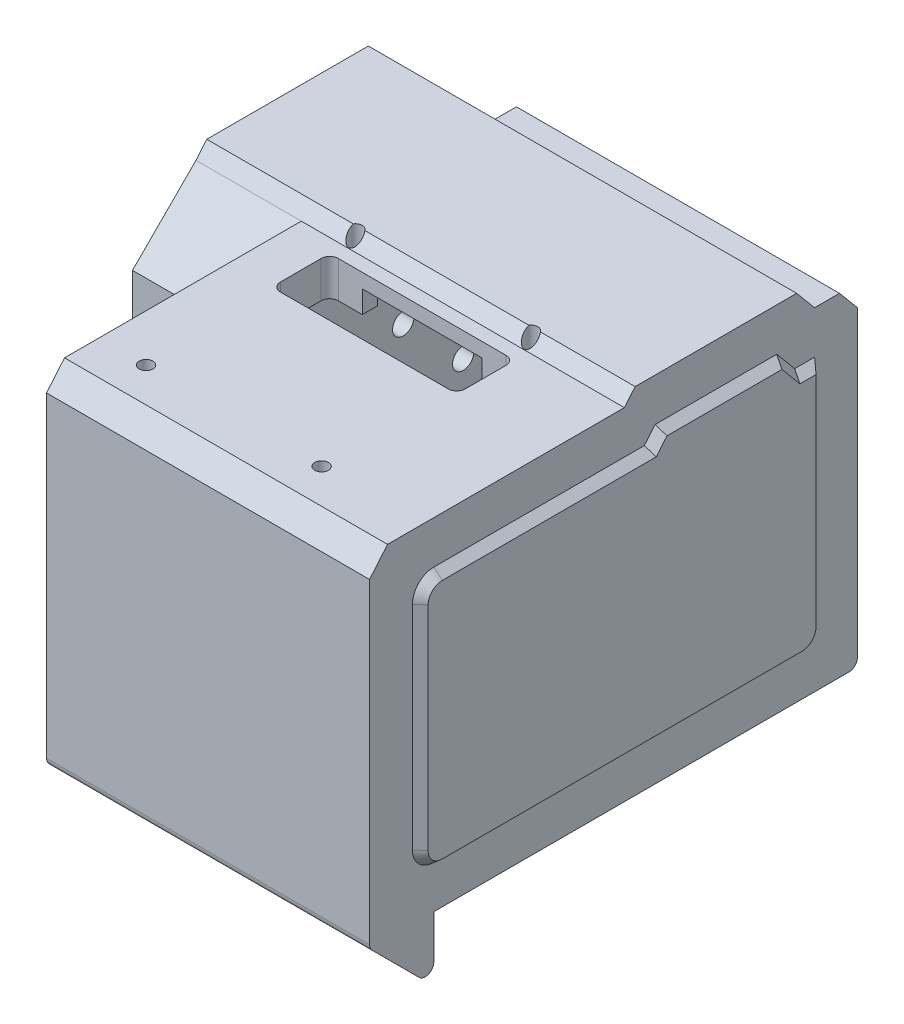
SolidWorks part; units mm, degrees
material "PLA"
ref_plane "Front Plane" through (0, 0, 0) normal (0, 0, 1) x (1, 0, 0)
ref_plane "Top Plane" through (0, 0, 0) normal (0, 1, 0) x (1, 0, 0)
ref_plane "Right Plane" through (0, 0, 0) normal (1, 0, 0) x (0, 0, -1)
sketch "Sketch1" plane through (0, 0, 0) normal (1, 0, 0) x (0, 0, -1)
  line L0 (-25.985, 0) -> (25.985, 0) construction
  line L1 (0, 21.625) -> (0, -21.625) construction
  line L7 (-25.985, -21.625) -> (25.985, -21.625)
  line L8 (-25.985, -21.625) -> (-25.985, 21.625)
  line L9 (-25.985, 21.625) -> (25.985, 21.625)
  line L10 (25.985, -21.625) -> (25.985, 21.625)
  point P5 (0, 0)
  dimension "D1" = 51.97
  dimension "D2" = 43.25
extrude "Boss-Extrude1" add sketch "Sketch1" along normal blind 3.175
sketch "Sketch2" plane through (3.175, 0, 0) normal (1, 0, 0) x (0, 0, -1)
  line L8 (-22.81, 18.45) -> (-22.81, -18.45)
  line L9 (-22.81, -18.45) -> (22.81, -18.45)
  line L10 (22.81, -18.45) -> (22.81, 18.45)
  line L11 (22.81, 18.45) -> (-22.81, 18.45)
  line L12 (-22.81, 18.45) -> (-22.81, -18.45)
  line L13 (-22.81, -18.45) -> (22.81, -18.45)
  line L14 (22.81, -18.45) -> (22.81, 18.45)
  line L15 (22.81, 18.45) -> (-22.81, 18.45)
  line L16 (-25.985, 21.625) -> (-25.985, -21.625)
  line L17 (-25.985, -21.625) -> (25.985, -21.625)
  line L18 (25.985, -21.625) -> (25.985, 21.625)
  line L19 (25.985, 21.625) -> (-25.985, 21.625)
  line L20 (-25.985, 21.625) -> (-25.985, -21.625)
  line L21 (-25.985, -21.625) -> (25.985, -21.625)
  line L22 (25.985, -21.625) -> (25.985, 21.625)
  line L23 (25.985, 21.625) -> (-25.985, 21.625)
  dimension "D1" = 3.175
  dimension "D2" = 0
extrude "Boss-Extrude2" add sketch "Sketch2" along normal blind 25.12
sketch "Sketch5" plane through (0, 18.45, 0) normal (0, -1, 0) x (1, 0, 0)
  line L0 (6.0285, -6.9385) -> (3.175, -6.9385)
  line L1 (25.4415, -6.9385) -> (28.295, -6.9385)
  line L4 (3.175, 22.81) -> (3.175, -22.81)
  line L5 (3.175, -22.81) -> (28.295, -22.81)
  line L6 (28.295, -22.81) -> (28.295, 22.81)
  line L7 (28.295, 22.81) -> (3.175, 22.81)
  line L8 (3.175, 22.81) -> (3.175, -6.9385)
  line L10 (28.295, -6.9385) -> (28.295, 22.81)
  line L11 (28.295, 22.81) -> (3.175, 22.81)
  line L36 (26.535, -2.15) -> (22.735, -2.15)
  line L37 (26.535, 4.625) -> (26.535, -2.15)
  line L38 (25.038, 4.625) -> (26.535, 4.625)
  line L39 (25.1773, 4.8479) -> (25.038, 4.625)
  line L40 (25.1773, 15.8031) -> (25.1773, 4.8479)
  line L41 (7.4927, 17.0031) -> (23.9773, 17.0031)
  line L42 (6.2927, 4.8479) -> (6.2927, 15.8031)
  line L43 (6.432, 4.625) -> (6.2927, 4.8479)
  line L44 (4.935, 4.625) -> (6.432, 4.625)
  line L45 (4.935, -2.15) -> (4.935, 4.625)
  line L46 (8.735, -2.15) -> (4.935, -2.15)
  line L47 (8.735, -3.9136) -> (8.735, -2.15)
  line L48 (4.375, -6.9385) -> (6.0285, -6.9385)
  line L49 (3.875, 20.2102) -> (3.875, -6.4385)
  line L50 (26.0951, 21.71) -> (5.3746, 21.71)
  line L51 (27.595, -6.4385) -> (27.595, 20.2105)
  line L52 (25.4415, -6.9385) -> (27.095, -6.9385)
  line L53 (22.735, -2.15) -> (22.735, -3.9136)
  line L54 (26.535, -2.15) -> (22.735, -2.15)
  line L55 (26.535, 4.625) -> (26.535, -2.15)
  line L56 (25.038, 4.625) -> (26.535, 4.625)
  line L57 (25.1773, 4.8479) -> (25.038, 4.625)
  line L58 (25.1773, 15.8031) -> (25.1773, 4.8479)
  line L59 (7.4927, 17.0031) -> (23.9773, 17.0031)
  line L60 (6.2927, 4.8479) -> (6.2927, 15.8031)
  line L61 (6.432, 4.625) -> (6.2927, 4.8479)
  line L62 (4.935, 4.625) -> (6.432, 4.625)
  line L63 (4.935, -2.15) -> (4.935, 4.625)
  line L64 (8.735, -2.15) -> (4.935, -2.15)
  line L65 (8.735, -3.9136) -> (8.735, -2.15)
  line L71 (22.735, -2.15) -> (22.735, -3.9136)
  arc A12 (25.1773, 15.8031) -> (23.9773, 17.0031) centre (23.9773, 15.8031) ccw
  arc A13 (7.4927, 17.0031) -> (6.2927, 15.8031) centre (7.4927, 15.8031) ccw
  arc A14 (8.735, -3.9136) -> (6.0285, -6.9385) centre (15.735, -12.9) ccw
  arc A15 (3.875, -6.4385) -> (4.375, -6.9385) centre (4.375, -6.4385) ccw
  arc A16 (27.095, -6.9385) -> (27.595, -6.4385) centre (27.095, -6.4385) ccw
  arc A17 (25.4415, -6.9385) -> (22.735, -3.9136) centre (15.735, -12.9) ccw
  arc A18 (25.1773, 15.8031) -> (23.9773, 17.0031) centre (23.9773, 15.8031) ccw
  arc A19 (7.4927, 17.0031) -> (6.2927, 15.8031) centre (7.4927, 15.8031) ccw
  arc A20 (8.735, -3.9136) -> (6.0285, -6.9385) centre (15.735, -12.9) ccw
  arc A23 (25.4415, -6.9385) -> (22.735, -3.9136) centre (15.735, -12.9) ccw
  circle A68 centre (5.485, -4.6) radius 0.8
  circle A69 centre (5.485, 19.85) radius 0.8
  circle A70 centre (25.985, 19.85) radius 0.8
  circle A71 centre (25.985, -4.6) radius 0.8
  spline S4 degree 3 poles (199.8506, -959.1962) (36.727, -55.2614) (14.0519, 23.473) (4.9866, 21.6619) (4.8913, 21.6332) (4.7098, 21.558) (4.6238, 21.5118) (4.4608, 21.403) (4.3836, 21.3399) (4.1763, 21.1325) (4.0645, 20.9654) (1.0086, 13.5957) (53.0588, -19.6485) (521.6785, 875.7094) knots -11.579327 -11.579327 -11.579327 -11.579327 0.125 0.125 0.25 0.25 0.375 0.375 0.5 0.5 0.75 0.75 10.719736 10.719736 10.719736 10.719736 only from (5.3746, 21.71) to (3.875, 20.2102)
  spline S5 degree 3 poles (-953.307, -174.2909) (-49.38, -11.1451) (29.3583, 11.5329) (27.5469, 20.5985) (27.5181, 20.6937) (27.443, 20.8752) (27.3968, 20.9612) (27.288, 21.1242) (27.2248, 21.2014) (27.0175, 21.4088) (26.8503, 21.5206) (19.4805, 24.5762) (-13.7629, -27.4761) (881.6326, -496.0119) knots -11.579675 -11.579675 -11.579675 -11.579675 0.125 0.125 0.25 0.25 0.375 0.375 0.5 0.5 0.75 0.75 10.719832 10.719832 10.719832 10.719832 only from (27.595, 20.2105) to (26.0951, 21.71)
  dimension "D3" = 1.6
  dimension "D1" = 0.2
  dimension "D2" = 0
extrude "Boss-Extrude4" add sketch "Sketch5" along normal blind 2.6
sketch "Sketch6" plane through (0, 18.45, 0) normal (0, -1, 0) x (1, 0, 0)
  line L1 (4.935, 4.625) -> (26.535, 4.625)
  line L2 (4.935, 4.625) -> (4.935, -2.15)
  line L3 (4.935, -2.15) -> (26.535, -2.15)
  line L4 (26.535, 4.625) -> (26.535, -2.15)
  line L18 (6.0285, -6.9385) -> (3.175, -6.9385)
  line L19 (3.175, -6.9385) -> (3.175, -22.81)
  line L20 (3.175, -22.81) -> (28.295, -22.81)
  line L21 (28.295, -22.81) -> (28.295, -6.9385)
  line L22 (28.295, -6.9385) -> (25.4415, -6.9385)
  line L23 (22.735, -3.9136) -> (22.735, -2.15)
  line L24 (22.735, -2.15) -> (26.535, -2.15)
  line L25 (26.535, -2.15) -> (26.535, 4.625)
  line L26 (26.535, 4.625) -> (25.038, 4.625)
  line L27 (25.038, 4.625) -> (25.1773, 4.8479)
  line L28 (25.1773, 4.8479) -> (25.1773, 15.8031)
  line L29 (23.9773, 17.0031) -> (7.4927, 17.0031)
  line L30 (6.2927, 15.8031) -> (6.2927, 4.8479)
  line L31 (6.2927, 4.8479) -> (6.432, 4.625)
  line L32 (6.432, 4.625) -> (4.935, 4.625)
  line L33 (4.935, 4.625) -> (4.935, -2.15)
  line L34 (4.935, -2.15) -> (8.735, -2.15)
  line L35 (8.735, -2.15) -> (8.735, -3.9136)
  line L42 (22.735, -2.15) -> (26.535, -2.15)
  line L43 (26.535, -2.15) -> (26.535, 4.625)
  line L44 (26.535, 4.625) -> (25.038, 4.625)
  line L50 (6.432, 4.625) -> (4.935, 4.625)
  line L51 (4.935, 4.625) -> (4.935, -2.15)
  line L52 (4.935, -2.15) -> (8.735, -2.15)
  arc A4 (8.735, -3.9136) -> (6.0285, -6.9385) centre (15.735, -12.9) ccw
  arc A5 (25.4415, -6.9385) -> (22.735, -3.9136) centre (15.735, -12.9) ccw
  arc A6 (25.1773, 15.8031) -> (23.9773, 17.0031) centre (23.9773, 15.8031) ccw
  arc A7 (7.4927, 17.0031) -> (6.2927, 15.8031) centre (7.4927, 15.8031) ccw
  line M35 (22.735, -2.15) -> (26.535, -2.15)
  line M36 (26.535, -2.15) -> (26.535, 4.625)
  line M37 (26.535, 4.625) -> (25.038, 4.625)
  line M45 (6.432, 4.625) -> (4.935, 4.625)
  line M46 (4.935, 4.625) -> (4.935, -2.15)
  line M47 (4.935, -2.15) -> (8.735, -2.15)
  dimension "D1" = 0
extrude "Cut-Extrude2" cut sketch "Sketch6" against normal through all contours L3 L1 M47 M35 M36 M37 M45 M46 region at (15.735, 18.45, 1.2375)
fillet "Fillet4" radius 1 4 edges at (26.535, 18.7375, -2.15) (26.535, 18.7375, 4.625) (4.935, 18.7375, -2.15) (4.935, 18.7375, 4.625)
sketch "Sketch7" plane through (0, 21.625, 0) normal (0, 1, 0) x (1, 0, 0)
  line L0 (28.295, 25.985) -> (28.295, -25.985) construction
  line L1 (0, -25.985) -> (28.295, -25.985)
  line L2 (0, -25.985) -> (0, 3.765)
  line L3 (0, 3.765) -> (28.295, 3.765)
  line L4 (28.295, -25.985) -> (28.295, 3.765)
  line M5 (25.535, -4.625) -> (5.935, -4.625)
  arc M6 (5.935, -4.625) -> (4.935, -3.625) centre (5.935, -3.625) cw
  line M7 (4.935, -3.625) -> (4.935, 1.15)
  arc M8 (4.935, 1.15) -> (5.935, 2.15) centre (5.935, 1.15) cw
  line M9 (5.935, 2.15) -> (25.535, 2.15)
  arc M10 (25.535, 2.15) -> (26.535, 1.15) centre (25.535, 1.15) cw
  line M11 (26.535, 1.15) -> (26.535, -3.625)
  arc M12 (26.535, -3.625) -> (25.535, -4.625) centre (25.535, -3.625) cw
  line M13 (0, 25.985) -> (0, -25.985)
  line M14 (0, -25.985) -> (28.295, -25.985)
  line M15 (28.295, -25.985) -> (28.295, 25.985)
  dimension "D1" = 29.75
extrude "Cut-Extrude3" cut sketch "Sketch7" against normal blind 1.5 contours L3 M13 M14 M15 M12 M5 M6 M7 M8 M9 M10 M11 region at (13.8158, 21.625, 13.1727)
chamfer "Chamfer3" distance 1.5 angle 40 1 edges at (14.1475, 21.625, -3.765) first distance on face at (14.1475, 20.875, -3.765)
chamfer "Chamfer4" distance 2.5 angle 40 1 edges at (14.1475, 20.125, 25.985) first distance on face at (14.1475, -0.75, 25.985)
chamfer "Chamfer5" distance 2.5 angle 40 1 edges at (14.1475, 21.625, -25.985) first distance on face at (14.1475, 0, -25.985)
sketch "Sketch8" plane through (0, -18.45, 0) normal (0, 1, 0) x (1, 0, 0)
  line L1 (8.535, 2.2774) -> (8.535, -21.2062)
  line L6 (22.935, -21.2062) -> (22.935, 2.2774)
  line L8 (5.6661, 6.9407) -> (3.175, 6.9407)
  line L11 (25.803, 6.9392) -> (28.295, 6.9392)
  line L16 (8.8158, -21.9777) -> (8.8158, -22.81)
  line L18 (22.6542, -21.9776) -> (22.6542, -22.81)
  line L19 (3.175, 22.81) -> (3.175, -22.81)
  line L20 (3.175, -22.81) -> (28.295, -22.81)
  line L21 (28.295, -22.81) -> (28.295, 22.81)
  line L22 (28.295, 22.81) -> (3.175, 22.81)
  line L23 (3.175, 6.9407) -> (3.175, -22.81)
  line L24 (3.175, -22.81) -> (8.8158, -22.81)
  line L25 (28.295, -22.81) -> (28.295, 6.9392)
  line L27 (22.6542, -22.81) -> (28.295, -22.81)
  arc A6 (5.6661, 6.9407) -> (9.0755, 3.2799) centre (15.735, 12.9) ccw
  arc A9 (9.0755, 3.2799) -> (8.535, 2.2774) centre (9.735, 2.2774) ccw
  arc A20 (8.535, -21.2062) -> (8.8158, -21.9777) centre (9.735, -21.2062) ccw
  arc A23 (22.6542, -21.9776) -> (22.935, -21.2062) centre (21.735, -21.2062) ccw
  arc A28 (22.935, 2.2774) -> (22.3945, 3.2799) centre (21.735, 2.2774) ccw
  arc A35 (22.3945, 3.2799) -> (25.803, 6.9392) centre (15.735, 12.9) ccw
  circle A56 centre (25.985, -16.1) radius 0.8
  circle A57 centre (5.485, 4.6) radius 0.8
  circle A58 centre (25.985, 4.6) radius 0.8
  circle A59 centre (5.485, -16.1) radius 0.8
  spline S5 degree 3 poles (5.6659, 6.9385) (5.666, 6.9385) (5.6664, 6.9383) (5.6671, 6.938) (5.6678, 6.9375) (5.6681, 6.9373) (5.6683, 6.9372) knots 0.329528 0.329528 0.329528 0.329528 0.414347 0.499166 0.583985 0.668804 0.668804 0.668804 0.668804
  line M1 (3.175, 22.81) -> (3.175, -22.81)
  line M2 (3.175, -22.81) -> (28.295, -22.81)
  line M3 (28.295, -22.81) -> (28.295, 22.81)
  dimension "D1" = 1.6
  dimension "D2" = 1.6
  dimension "D3" = 1.6
  dimension "D4" = 1.6
  dimension "D5" = 0
extrude "Boss-Extrude5" add sketch "Sketch8" along normal blind 1.9 contours A20 L1 A9 A6 L8 L16 A59 A57 M1 M2 | A35 A28 L6 A23 L18 L11 A58 A56 M2 M3 region at (5.8173, -18.45, 8.4819) region at (25.6526, -18.45, 8.4823)
sketch "Sketch9" plane through (0, 18.45, 0) normal (0, -1, 0) x (1, 0, 0)
  circle A0 centre (5.485, -4.6) radius 0.8 construction
  circle A1 centre (25.985, -4.6) radius 0.8 construction
  circle A2 centre (25.985, 19.85) radius 0.8 construction
  circle A3 centre (5.485, 19.85) radius 0.8 construction
  circle A4 centre (5.485, -4.6) radius 0.8
  circle A5 centre (25.985, -4.6) radius 0.8
  circle A6 centre (25.985, 19.85) radius 0.8
  circle A7 centre (5.485, 19.85) radius 0.8
extrude "Cut-Extrude4" cut sketch "Sketch9" against normal through all
sketch "Sketch10" plane through (0, -21.625, 0) normal (0, -1, 0) x (1, 0, 0)
  line L0 (28.295, 25.985) -> (28.295, -25.985) construction
  line L1 (0, 25.985) -> (28.295, 25.985)
  line L2 (0, 25.985) -> (0, -6.935)
  line L3 (0, -6.935) -> (28.295, -6.935)
  line L4 (28.295, 25.985) -> (28.295, -6.935)
  dimension "D1" = 32.92
extrude "Cut-Extrude5" cut sketch "Sketch10" against normal blind 1.9
chamfer "Chamfer6" distance 1.9 angle 40 1 edges at (14.1475, -19.725, -6.935) first distance on face at (14.1475, -20.675, -6.935)
sketch "Sketch11" plane through (0, -18.45, 0) normal (0, 1, 0) x (1, 0, 0)
  line L10 (3.175, 22.81) -> (3.175, 6.9407)
  line L11 (3.175, 6.9407) -> (5.6661, 6.9407)
  line L12 (8.535, 2.2774) -> (8.535, -21.2062)
  line L13 (8.8158, -21.9777) -> (8.8158, -22.81)
  line L14 (8.8158, -22.81) -> (22.6542, -22.81)
  line L15 (22.6542, -22.81) -> (22.6542, -21.9776)
  line L16 (22.935, -21.2062) -> (22.935, 2.2774)
  line L17 (25.803, 6.9392) -> (28.295, 6.9392)
  line L18 (28.295, 6.9392) -> (28.295, 22.81)
  line L19 (28.295, 22.81) -> (3.175, 22.81)
  line L20 (3.175, 22.81) -> (3.175, 6.9407)
  line L21 (3.175, 6.9407) -> (5.6661, 6.9407)
  line L27 (25.803, 6.9392) -> (28.295, 6.9392)
  line L28 (28.295, 6.9392) -> (28.295, 22.81)
  line L29 (28.295, 22.81) -> (3.175, 22.81)
  arc A0 (9.0755, 3.2799) -> (22.3945, 3.2799) centre (15.735, 9.9394) ccw
  arc A6 (5.6661, 6.9407) -> (9.0755, 3.2799) centre (15.735, 12.9) ccw
  arc A7 (9.0755, 3.2799) -> (8.535, 2.2774) centre (9.735, 2.2774) ccw
  arc A8 (8.535, -21.2062) -> (8.8158, -21.9777) centre (9.735, -21.2062) ccw
  arc A9 (22.6542, -21.9776) -> (22.935, -21.2062) centre (21.735, -21.2062) ccw
  arc A10 (22.935, 2.2774) -> (22.3945, 3.2799) centre (21.735, 2.2774) ccw
  arc A11 (22.3945, 3.2799) -> (25.803, 6.9392) centre (15.735, 12.9) ccw
  arc A12 (5.6661, 6.9407) -> (9.0755, 3.2799) centre (15.735, 12.9) ccw
  arc A17 (22.3945, 3.2799) -> (25.803, 6.9392) centre (15.735, 12.9) ccw
  dimension "D1" = 0
extrude "Cut-Extrude6" cut sketch "Sketch11" against normal through all
sketch "Sketch12" plane through (0, -18.45, 0) normal (0, 1, 0) x (1, 0, 0)
  circle A0 centre (25.985, 4.6) radius 0.8 construction
  circle A1 centre (25.985, -16.1) radius 0.8 construction
  circle A2 centre (5.485, -16.1) radius 0.8 construction
  circle A3 centre (5.485, 4.6) radius 0.8 construction
  circle A4 centre (25.985, 4.6) radius 0.8
  circle A5 centre (25.985, -16.1) radius 0.8
  circle A6 centre (5.485, -16.1) radius 0.8
  circle A7 centre (5.485, 4.6) radius 0.8
extrude "Cut-Extrude7" cut sketch "Sketch12" against normal through all
sketch "Sketch13" plane through (0, -21.625, 0) normal (0, -1, 0) x (1, 0, 0)
  line L0 (28.295, -5.3407) -> (28.295, 25.985) construction
  line L1 (0, -25.985) -> (28.295, -25.985)
  line L2 (0, -25.985) -> (0, 7.0246)
  line L3 (0, 7.0246) -> (28.295, 7.0246)
  line L4 (28.295, -25.985) -> (28.295, 7.0246)
extrude "Cut-Extrude8" cut sketch "Sketch13" against normal up to surface (1.9 mm away) up to face at (15.2058, -19.725, 0.7228)
sketch "Sketch14" plane through (28.295, 0, 0) normal (1, 0, 0) x (0, 0, -1)
  line L0 (6.9392, -16.55) -> (22.81, -16.55)
  line L1 (6.9392, -19.725) -> (22.81, -19.725)
  line L3 (6.9392, -16.55) -> (22.81, -16.55)
  line L5 (6.9392, -19.725) -> (22.81, -19.725)
  line L16 (-25.985, -19.725) -> (6.9392, -19.725)
  line L17 (6.9392, -19.725) -> (6.9392, -16.55)
  line L18 (6.9392, -16.55) -> (-22.81, -16.55)
  line L19 (-22.81, -16.55) -> (-22.81, 15.85)
  line L20 (-22.81, 15.85) -> (6.9385, 15.85)
  line L21 (6.9385, 15.85) -> (6.9385, 18.45)
  line L22 (6.9385, 18.45) -> (22.81, 18.45)
  line L23 (22.81, 18.45) -> (22.81, -19.725)
  line L24 (22.81, -19.725) -> (25.985, -19.725)
  line L25 (25.985, -19.725) -> (25.985, 19.125)
  line L26 (25.985, 19.125) -> (23.8873, 21.625)
  line L27 (23.8873, 21.625) -> (5.0236, 21.625)
  line L28 (5.0236, 21.625) -> (3.765, 20.125)
  line L29 (3.765, 20.125) -> (-23.8873, 20.125)
  line L30 (-23.8873, 20.125) -> (-25.985, 17.625)
  line L31 (-25.985, 17.625) -> (-25.985, -19.725)
  line L32 (-25.985, -19.725) -> (6.9392, -19.725)
  line L34 (6.9392, -16.55) -> (-22.81, -16.55)
  line L35 (-22.81, -16.55) -> (-22.81, 15.85)
  line L36 (-22.81, 15.85) -> (6.9385, 15.85)
  line L37 (6.9385, 15.85) -> (6.9385, 18.45)
  line L38 (6.9385, 18.45) -> (22.81, 18.45)
  line L39 (22.81, 18.45) -> (22.81, -16.55)
  line L40 (22.81, -19.725) -> (25.985, -19.725)
  line L41 (25.985, -19.725) -> (25.985, 19.125)
  line L42 (25.985, 19.125) -> (23.8873, 21.625)
  line L43 (23.8873, 21.625) -> (5.0236, 21.625)
  line L44 (5.0236, 21.625) -> (3.765, 20.125)
  line L45 (3.765, 20.125) -> (-23.8873, 20.125)
  line L46 (-23.8873, 20.125) -> (-25.985, 17.625)
  line L47 (-25.985, 17.625) -> (-25.985, -19.725)
  line M21 (-25.985, -19.725) -> (6.9392, -19.725)
  line M22 (6.9392, -19.725) -> (6.9392, -16.55)
  line M23 (6.9392, -16.55) -> (-22.81, -16.55)
  line M24 (-22.81, -16.55) -> (-22.81, 15.85)
  line M25 (-22.81, 15.85) -> (6.9385, 15.85)
  line M26 (6.9385, 15.85) -> (6.9385, 18.45)
  line M27 (6.9385, 18.45) -> (22.81, 18.45)
  line M28 (22.81, 18.45) -> (22.81, -19.725)
  line M29 (22.81, -19.725) -> (25.985, -19.725)
  line M30 (25.985, -19.725) -> (25.985, 19.125)
  line M31 (25.985, 19.125) -> (23.8873, 21.625)
  line M32 (23.8873, 21.625) -> (5.0236, 21.625)
  line M33 (5.0236, 21.625) -> (3.765, 20.125)
  line M34 (3.765, 20.125) -> (-23.8873, 20.125)
  line M35 (-23.8873, 20.125) -> (-25.985, 17.625)
  line M36 (-25.985, 17.625) -> (-25.985, -19.725)
  dimension "D1" = 0
extrude "Boss-Extrude6" add sketch "Sketch14" along normal blind 3.175 contours M36 M21 M22 M23 M24 M25 M26 M27 M28 M29 M30 M31 M32 M33 M34 M35 | L1 L0 M22 M28 | L40 L41 L42 L43 L44 L45 L46 L47 L32 L1 region at (28.295, -18.1375, -14.8746) region at (28.295, -18.1375, -6.275)
sketch "Sketch15" plane through (31.47, 0, 0) normal (1, 0, 0) x (0, 0, -1)
  line L0 (25.985, 0) -> (12.495, 0) construction
  line L1 (25.985, -19.725) -> (25.985, 19.125) construction
  circle A0 centre (12.495, 0) radius 10
  circle A1 centre (12.495, 0) radius 7 construction
  circle A2 centre (12.495, 7) radius 1.25
  circle A3 centre (19.495, 0) radius 1.25
  circle A4 centre (5.495, 0) radius 1.25
  circle A5 centre (12.495, -7) radius 1.25
  dimension "D2" = 20
  dimension "D3" = 14
  dimension "D4" = 2.5
  dimension "D1" = 13.49
extrude "Boss-Extrude7" add sketch "Sketch15" along normal blind 12.7
sketch "Sketch16" plane through (31.47, 0, 0) normal (1, 0, 0) x (0, 0, -1)
  circle A0 centre (19.495, 0) radius 1.25 construction
  circle A1 centre (12.495, -7) radius 1.25 construction
  circle A2 centre (5.495, 0) radius 1.25 construction
  circle A3 centre (12.495, 7) radius 1.25 construction
  circle A4 centre (19.495, 0) radius 1.25
  circle A5 centre (12.495, -7) radius 1.25
  circle A6 centre (5.495, 0) radius 1.25
  circle A7 centre (12.495, 7) radius 1.25
extrude "Cut-Extrude9" cut sketch "Sketch16" against normal up to surface (3.175 mm away) up to face at (28.295, -0.4938, -3.4694)
sketch "Sketch17" plane through (31.47, 0, 0) normal (1, 0, 0) x (0, 0, -1)
  line L1 (-0.4777, -16.55) -> (22.81, -16.55)
  line L2 (22.81, -16.55) -> (22.81, 17.9694)
  line L3 (22.81, 17.9694) -> (22.4067, 18.45)
  line L4 (22.4067, 18.45) -> (6.5042, 18.45)
  line L5 (6.5042, 18.45) -> (5.2455, 16.95)
  line L8 (-25.985, 17.625) -> (-25.985, -19.725)
  line L9 (-25.985, -19.725) -> (25.985, -19.725)
  line L10 (25.985, -19.725) -> (25.985, 19.125)
  line L11 (25.985, 19.125) -> (23.8873, 21.625)
  line L12 (23.8873, 21.625) -> (5.0236, 21.625)
  line L13 (5.0236, 21.625) -> (3.765, 20.125)
  line L14 (3.765, 20.125) -> (-23.8873, 20.125)
  line L15 (-23.8873, 20.125) -> (-25.985, 17.625)
  line L18 (25.985, -19.725) -> (25.985, 19.125)
  line L19 (25.985, 19.125) -> (23.8873, 21.625)
  line L20 (23.8873, 21.625) -> (5.0236, 21.625)
  line L21 (5.0236, 21.625) -> (3.765, 20.125)
  line L24 (5.2455, 16.95) -> (-0.4777, 10.6655)
  line L25 (-0.4777, 10.6655) -> (-0.4777, -16.55)
  line L26 (-3.6527, -16.55) -> (-3.6527, -19.725)
  line L27 (-3.6527, 11.6724) -> (-3.6527, -16.55)
  line L28 (3.765, 20.125) -> (-3.6527, 12.7073)
  line L29 (5.2455, 16.95) -> (-22.4067, 16.95) construction
  line L30 (-3.6527, 12.7073) -> (-3.6527, 11.6724)
  line L31 (-22.81, -16.55) -> (22.81, -16.55) construction
  line L32 (3.765, 20.125) -> (-23.8873, 20.125) construction
  line L33 (-23.8873, 20.125) -> (-25.985, 17.625) construction
  line L34 (-25.985, 17.625) -> (-25.985, -19.725) construction
  line L35 (-22.81, 16.4694) -> (-22.81, -16.55) construction
  line L36 (-22.4067, 16.95) -> (-22.81, 16.4694) construction
  line L37 (-25.985, -19.725) -> (25.985, -19.725) construction
  line L38 (-25.985, -19.725) -> (25.985, -19.725) construction
  line L39 (-3.6527, -19.725) -> (25.985, -19.725)
  dimension "D3" = 8.5
  dimension "D4" = 3.175
  dimension "D1" = 0
  dimension "D2" = 3.175
extrude "Boss-Extrude8" add sketch "Sketch17" along normal blind 12.3
sketch "Sketch18" plane through (0, 0, 0) normal (-1, 0, 0) x (0, 0, 1)
  line L8 (-25.985, 19.125) -> (-25.985, -19.725)
  line L9 (-25.985, -19.725) -> (25.985, -19.725)
  line L10 (25.985, -19.725) -> (25.985, 17.625)
  line L11 (25.985, 17.625) -> (23.8873, 20.125)
  line L12 (23.8873, 20.125) -> (-3.765, 20.125)
  line L13 (-3.765, 20.125) -> (-5.0236, 21.625)
  line L14 (-5.0236, 21.625) -> (-23.8873, 21.625)
  line L15 (-23.8873, 21.625) -> (-25.985, 19.125)
  line L16 (-25.985, 19.125) -> (-25.985, -19.725)
  line L17 (-25.985, -19.725) -> (25.985, -19.725)
  line L18 (25.985, -19.725) -> (25.985, 17.625)
  line L19 (25.985, 17.625) -> (23.8873, 20.125)
  line L20 (23.8873, 20.125) -> (-3.765, 20.125)
  line L21 (-3.765, 20.125) -> (-5.0236, 21.625)
  line L22 (-5.0236, 21.625) -> (-23.8873, 21.625)
  line L23 (-23.8873, 21.625) -> (-25.985, 19.125)
  dimension "D1" = 0
extrude "Boss-Extrude9" add sketch "Sketch18" along normal blind 6.25
sketch "Sketch19" plane through (-6.25, 0, 0) normal (-1, 0, 0) x (0, 0, 1)
  line L0 (-25.985, 19.125) -> (-30.985, 19.125)
  line L1 (-30.985, 19.125) -> (-30.985, -19.725)
  line L2 (-30.985, -19.725) -> (-25.985, -19.725)
  line L3 (-25.985, -19.725) -> (-25.985, 19.125)
  dimension "D1" = 5
extrude "Boss-Extrude10" add sketch "Sketch19" against normal up to surface (37.72 mm away) up to face at (31.47, 5.1887, 13.2329)
chamfer "Chamfer7" distance 2.5 angle 40 1 edges at (12.61, 19.125, -30.985) first distance on face at (12.61, -0.3, -30.985)
sketch "Sketch20" plane through (-6.25, 0, 0) normal (-1, 0, 0) x (0, 0, 1)
  line L38 (-25.985, 14.125) -> (-25.985, -14.725)
  line L39 (-25.985, -14.725) -> (20.985, -14.725)
  line L40 (20.985, -14.725) -> (20.985, 15.125)
  line L41 (20.985, 15.125) -> (-6.0965, 15.125)
  line L42 (-6.0965, 15.125) -> (-7.3552, 16.625)
  line L43 (-7.3552, 16.625) -> (-21.5557, 16.625)
  line L44 (-21.5557, 16.625) -> (-23.6535, 14.125)
  line L45 (-23.6535, 14.125) -> (-25.985, 14.125)
  line L46 (-25.985, 14.125) -> (-25.985, -12.225)
  line L47 (-23.485, -14.725) -> (18.485, -14.725)
  line L48 (20.985, -12.225) -> (20.985, 12.625)
  line L49 (18.485, 15.125) -> (-6.0965, 15.125)
  line L50 (-6.0965, 15.125) -> (-7.3552, 16.625)
  line L51 (-7.3552, 16.625) -> (-21.5557, 16.625)
  line L52 (-21.5557, 16.625) -> (-23.6535, 14.125)
  line L53 (-23.6535, 14.125) -> (-25.985, 14.125)
  arc A8 (-25.985, -12.225) -> (-23.485, -14.725) centre (-23.485, -12.225) ccw
  arc A9 (18.485, -14.725) -> (20.985, -12.225) centre (18.485, -12.225) ccw
  arc A10 (20.985, 12.625) -> (18.485, 15.125) centre (18.485, 12.625) ccw
  dimension "D2" = 2.5
  dimension "D1" = 5
extrude "Boss-Extrude11" add sketch "Sketch20" along normal blind 1
chamfer "Chamfer8" distance 1 angle 40 11 edges at (-7.25, 0.95, -25.985) (-7.25, 14.125, -24.8192) (-7.25, 15.375, -22.6046) (-7.25, 16.625, -14.4555) (-7.25, 15.875, -6.7259) (-7.25, 15.125, 6.1942) (-7.25, 14.3928, 20.2528) (-7.25, 0.2, 20.985) (-7.25, -13.9928, 20.2528) (-7.25, -14.725, -2.5) (-7.25, -13.9928, -25.2528) first distance on face at (-6.75, 0.95, -25.985) first distance on face at (-6.75, 14.125, -24.8192) first distance on face at (-6.75, 15.375, -22.6046) first distance on face at (-6.75, 16.625, -14.4555) first distance on face at (-6.75, 15.875, -6.7259) first distance on face at (-6.75, 15.125, 6.1942) first distance on face at (-6.75, 14.1339, 19.9939) first distance on face at (-6.75, 0.2, 20.985) first distance on face at (-6.75, -13.7339, 19.9939) first distance on face at (-6.75, -14.725, -2.5) first distance on face at (-6.75, -13.7339, -24.9939)
sketch "Sketch21" plane through (0, -16.55, 0) normal (0, 1, 0) x (1, 0, 0)
  line L0 (3.175, -7.9346) -> (28.295, -7.9354)
  line L5 (5.6661, 6.9407) -> (3.175, 6.9407)
  line L6 (3.175, 6.9407) -> (3.175, -22.81)
  line L7 (3.175, -22.81) -> (8.8158, -22.81)
  line L8 (8.8158, -22.81) -> (8.8158, -21.9777)
  line L9 (8.535, -21.2062) -> (8.535, 2.2774)
  line L10 (5.6661, 6.9407) -> (3.175, 6.9407)
  line L11 (3.175, 6.9407) -> (3.175, -7.9346)
  line L15 (22.935, 2.2774) -> (22.935, -21.2062)
  line L16 (22.6542, -21.9776) -> (22.6542, -22.81)
  line L17 (22.6542, -22.81) -> (28.295, -22.81)
  line L18 (28.295, -22.81) -> (28.295, 6.9392)
  line L19 (28.295, 6.9392) -> (25.803, 6.9392)
  line L23 (28.295, -7.9354) -> (28.295, 6.9392)
  line L24 (28.295, 6.9392) -> (25.803, 6.9392)
  line L25 (8.535, 2.2774) -> (8.535, -21.2062)
  line L26 (8.8158, -21.9777) -> (8.8158, -22.81)
  line L27 (8.8158, -22.81) -> (22.6542, -22.81)
  line L28 (22.6542, -22.81) -> (22.6542, -21.9776)
  line L29 (22.935, -21.2062) -> (22.935, 2.2774)
  arc A3 (5.6661, 6.9407) -> (9.0755, 3.2799) centre (15.735, 12.9) ccw
  arc A4 (8.535, -21.2062) -> (8.8158, -21.9777) centre (9.735, -21.2062) ccw
  arc A5 (9.0755, 3.2799) -> (8.535, 2.2774) centre (9.735, 2.2774) ccw
  arc A6 (5.6661, 6.9407) -> (9.0755, 3.2799) centre (15.735, 12.9) ccw
  arc A9 (22.3945, 3.2799) -> (25.803, 6.9392) centre (15.735, 12.9) ccw
  arc A10 (22.935, 2.2774) -> (22.3945, 3.2799) centre (21.735, 2.2774) ccw
  arc A11 (22.6542, -21.9776) -> (22.935, -21.2062) centre (21.735, -21.2062) ccw
  arc A12 (22.3945, 3.2799) -> (25.803, 6.9392) centre (15.735, 12.9) ccw
  arc A17 (9.0755, 3.2799) -> (22.3945, 3.2799) centre (15.735, 9.9394) ccw
  arc A18 (9.0755, 3.2799) -> (8.535, 2.2774) centre (9.735, 2.2774) ccw
  arc A19 (8.535, -21.2062) -> (8.8158, -21.9777) centre (9.735, -21.2062) ccw
  arc A20 (22.6542, -21.9776) -> (22.935, -21.2062) centre (21.735, -21.2062) ccw
  arc A21 (22.935, 2.2774) -> (22.3945, 3.2799) centre (21.735, 2.2774) ccw
  arc A22 (9.0755, 3.2799) -> (22.3945, 3.2799) centre (15.735, 9.9394) ccw
  dimension "D1" = 0
  dimension "D2" = 0
  dimension "D3" = 0
extrude "Cut-Extrude10" cut sketch "Sketch21" against normal through all
chamfer "Chamfer9" distance 6.35 angle 45 1 edges at (15.735, -19.725, -22.81)
sketch "Sketch22" plane through (31.47, 0, 0) normal (1, 0, 0) x (0, 0, -1)
  line L0 (-25.985, -19.725) -> (-18.485, -27.225)
  line L1 (-18.485, -27.225) -> (-18.485, -19.725)
  line L2 (-25.985, -19.725) -> (-3.6527, -19.725) construction
  line L3 (-18.485, -19.725) -> (-25.985, -19.725)
  dimension "D1" = 45
  dimension "D2" = 7.5
extrude "Boss-Extrude12" add sketch "Sketch22" against normal up to surface (37.72 mm away) up to face at (-6.25, 11.655, -7.3661)
fillet "Fillet5" radius 1 2 edges at (12.61, -19.725, -30.985) (12.61, -19.725, 25.985)
fillet "Fillet6" radius 1 1 edges at (12.61, -27.225, 18.485)
ref_plane "Plane1" through (-16.25, 0, 0) normal (-1, 0, 0) x (0, 0, 1)
mirror "Mirror2" about plane through (-16.25, 0, 0) normal (-1, 0, 0) of bodies 122
delete or keep bodies "Body-Delete/Keep 1" type delete bodies bodies 122
